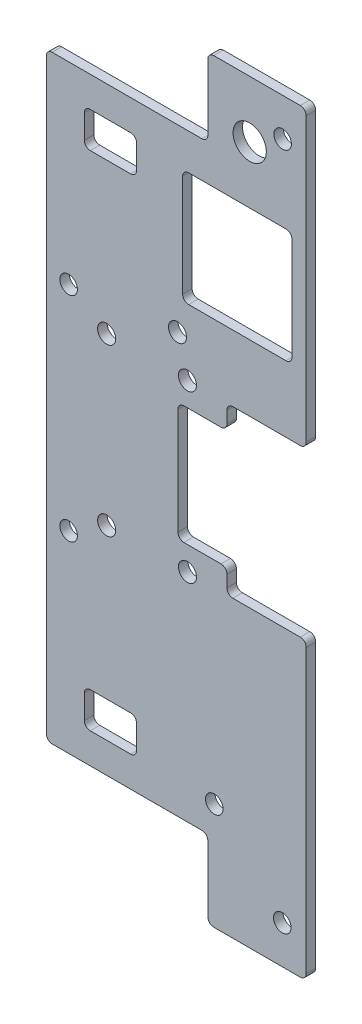
SolidWorks part; units mm, degrees
material "Thornel Mat VMA"
ref_plane "Front Plane" through (0, 0, 0) normal (0, 0, 1) x (1, 0, 0)
ref_plane "Top Plane" through (0, 0, 0) normal (0, 1, 0) x (1, 0, 0)
ref_plane "Right Plane" through (0, 0, 0) normal (1, 0, 0) x (0, 0, -1)
sketch "Sketch1" plane through (0, 0, 0) normal (0, 0, 1) x (1, 0, 0)
  line L0 (-2.9301, -104.5098) -> (-3.3149, -104.5098)
  line L1 (-3.3149, -72.8868) -> (-2.9301, -72.8868)
  line L78 (45.3299, -66.5368) -> (45.3299, -72.8868)
  line L79 (45.3299, -104.5098) -> (45.3299, -110.8598)
  line L80 (66.5174, -66.5368) -> (105.3971, 12.1397)
  line L81 (105.3971, 12.1397) -> (38.7094, 12.1397)
  line L88 (38.7094, 12.1397) -> (38.7094, -8.6883)
  line L89 (-2.9301, -8.6883) -> (38.7094, -8.6883)
  line L90 (-3.3149, -53.8368) -> (-2.9301, -53.8368)
  line L91 (-2.9301, -53.8368) -> (-2.9301, -8.6883)
  line L92 (-3.3149, -66.5368) -> (-3.3149, -53.8368)
  line L93 (-3.3149, -72.8868) -> (-3.3149, -66.5368)
  line L94 (-2.9301, -104.5098) -> (-2.9301, -72.8868)
  line L95 (-3.3149, -110.8598) -> (-3.3149, -104.5098)
  line L96 (66.5174, -110.8598) -> (105.3971, -189.5363)
  line L97 (105.3971, -189.5363) -> (38.7094, -189.5363)
  line L98 (38.7094, -189.5363) -> (38.7094, -168.7083)
  line L99 (-2.9301, -168.7083) -> (38.7094, -168.7083)
  line L106 (-3.3149, -110.8598) -> (-3.3149, -123.5598)
  line L107 (-3.3149, -123.5598) -> (-2.9301, -123.5598)
  line L108 (66.5174, -110.8598) -> (45.3299, -110.8598)
  line L109 (45.3299, -66.5368) -> (66.5174, -66.5368)
  line L110 (45.3299, -104.5098) -> (45.3299, -72.8868)
  line L111 (-2.9301, -123.5598) -> (-2.9301, -168.7083)
  circle A0 centre (90.6739, 2.6147) radius 2.3495
  circle A1 centre (41.9566, -16.4353) radius 2.3495
  circle A2 centre (3.0351, -60.1868) radius 2.3495
  circle A3 centre (3.0351, -117.2098) radius 2.3495
  circle A4 centre (41.9566, -160.9613) radius 2.3495
  circle A5 centre (90.6739, -180.0113) radius 2.3495
  circle A6 centre (51.4094, -3.1003) radius 4.445
  point P2 (90.6739, 2.6147)
  point P4 (41.9566, -16.4353)
  point P6 (3.0351, -60.1868)
  point P8 (3.0351, -117.2098)
  point P10 (41.9566, -160.9613)
  point P11 (90.6739, -180.0113)
  dimension "D2" = 4.699
  dimension "D5" = 8.89
  dimension "D1" = 66.6876
  dimension "D3" = 12.7
  dimension "D4" = 15.24
  dimension "D6" = 48.26
extrude "Boss-Extrude1" add sketch "Sketch1" along normal blind 2.54
sketch "Sketch2" plane through (0, 0, 2.54) normal (0, 0, 1) x (1, 0, 0)
  line L0 (-3.3149, -53.8368) -> (-3.3149, -72.8868) construction
  line L1 (45.3299, -66.5368) -> (66.5174, -66.5368) construction
  line L2 (45.3299, -88.6983) -> (-2.9301, -88.6983) construction
  line L3 (45.3299, -110.8598) -> (45.3299, -66.5368) construction
  line L4 (-2.9301, -72.8868) -> (-2.9301, -104.5098) construction
  circle A0 centre (13.1951, -66.5368) radius 2.413
  circle A2 centre (34.7851, -66.5368) radius 2.413
  circle A4 centre (34.7851, -110.8598) radius 2.413
  circle A6 centre (13.1951, -110.8598) radius 2.413
  dimension "D1" = 4.826
  dimension "D2" = 21.59
  dimension "D3" = 4.826
  dimension "D5" = 16.51
  dimension "D7" = 0
extrude "Cut-Extrude1" cut sketch "Sketch2" against normal through all
sketch "Sketch3" plane through (0, 0, 2.54) normal (0, 0, 1) x (1, 0, 0)
  line L0 (45.3299, -110.8598) -> (45.3299, -66.5368) construction
  line L1 (45.3299, -72.8868) -> (32.2451, -72.8868)
  line L2 (45.3299, -72.8868) -> (45.3299, -104.5098)
  line L3 (45.3299, -104.5098) -> (32.2451, -104.5098)
  line L4 (32.2451, -72.8868) -> (32.2451, -104.5098)
  line L5 (45.3299, -66.5368) -> (66.5174, -66.5368) construction
  line L6 (66.5174, -110.8598) -> (45.3299, -110.8598) construction
  circle A1 centre (13.1951, -66.5368) radius 2.413 construction
  dimension "D3" = 19.05
  dimension "D1" = 6.35
  dimension "D2" = 6.35
extrude "Cut-Extrude2" cut sketch "Sketch3" against normal through all
sketch "Sketch4" plane through (0, 0, 2.54) normal (0, 0, 1) x (1, 0, 0)
  line L0 (-2.9301, -168.7083) -> (38.7094, -168.7083) construction
  line L1 (27.4577, 15.7469) -> (40.2334, 15.7469)
  line L2 (27.4577, 15.7469) -> (27.4577, -8.6883)
  line L3 (27.4577, -8.6883) -> (40.2334, -8.6883)
  line L4 (40.2334, 15.7469) -> (40.2334, -8.6883)
  line L5 (0, -197.042) -> (40.2334, -197.042)
  line L6 (0, -197.042) -> (0, -168.7083)
  line L7 (0, -168.7083) -> (40.2334, -168.7083)
  line L8 (40.2334, -197.042) -> (40.2334, -168.7083)
  line L9 (38.7094, -168.7083) -> (38.7094, -189.5363) construction
  line L10 (38.7094, -8.6883) -> (-2.9301, -8.6883) construction
  dimension "D1" = 1.524
extrude "Cut-Extrude3" cut sketch "Sketch4" against normal through all
sketch "Sketch5" plane through (0, 0, 0) normal (0, 0, -1) x (-1, 0, 0)
  line L0 (2.9301, -8.6883) -> (2.9301, -53.8368) construction
  line L1 (-40.2334, -8.6883) -> (2.9301, -8.6883) construction
  circle A0 centre (-32.1219, -22.4043) radius 2.413
  circle A1 centre (-32.1219, -56.6943) radius 2.413
  dimension "D4" = 4.826
  dimension "D1" = 35.052
  dimension "D2" = 13.716
  dimension "D3" = 34.29
extrude "Cut-Extrude4" cut sketch "Sketch5" against normal through all
sketch "Sketch7" plane through (0, 0, 2.54) normal (0, 0, 1) x (1, 0, 0)
  line L0 (66.5174, -66.5368) -> (66.5174, 21.5221)
  line L1 (66.5174, 21.5221) -> (127.8208, 21.5221)
  line L2 (66.5174, -110.8598) -> (66.5174, -200.2563)
  line L3 (66.5174, -200.2563) -> (115.7822, -200.2563)
  line L4 (115.7822, -200.2563) -> (127.8208, 21.5221)
  line L5 (66.5174, -66.5368) -> (66.5174, -110.8598)
extrude "Cut-Extrude5" cut sketch "Sketch7" against normal through all both and the other way through all
extrude "Cut-Extrude6" cut sketch "Sketch8" against normal through all
sketch "Sketch8" plane through (7.0946, -169.3164, 0) normal (0, 0, -1) x (0.9999, -0.0134, 0)
  circle A0 centre (50.8264, -172.0317) radius 2.3495
  circle A1 centre (53.1547, 9.3081) radius 2.3495
fillet "Fillet1" radius 1.5875 16 edges at (-2.9301, -168.7083, 1.27) (40.2334, -168.7083, 1.27) (40.2334, -189.5363, 1.27) (66.5174, -189.5363, 1.27) (66.5174, -110.8598, 1.27) (45.3299, -110.8598, 1.27) (45.3299, -104.5098, 1.27) (32.2451, -104.5098, 1.27) (32.2451, -72.8868, 1.27) (45.3299, -72.8868, 1.27) (45.3299, -66.5368, 1.27) (66.5174, -66.5368, 1.27) (66.5174, 12.1397, 1.27) (40.2334, 12.1397, 1.27) (40.2334, -8.6883, 1.27) (-2.9301, -8.6883, 1.27)
sketch "Sketch9" plane through (0, -123.5598, 0) normal (0, -1, 0) x (1, 0, 0)
  line L1 (-3.3149, 2.54) -> (-2.9301, 2.54)
  line L2 (-3.3149, 2.54) -> (-3.3149, 0)
  line L3 (-3.3149, 0) -> (-2.9301, 0)
  line L4 (-2.9301, 2.54) -> (-2.9301, 0)
extrude "Cut-Extrude7" cut sketch "Sketch9" against normal through all
sketch "Sketch10" plane through (0, 0, 0) normal (0, 0, -1) x (-1, 0, 0)
  line L0 (-40.2334, -7.1008) -> (-40.2334, 10.5522) construction
  line L1 (-33.4974, -18.3403) -> (-62.7074, -18.3403)
  line L2 (-33.4974, -18.3403) -> (-33.4974, -48.8203)
  line L3 (-33.4974, -48.8203) -> (-62.7074, -48.8203)
  line L4 (-62.7074, -18.3403) -> (-62.7074, -48.8203)
  line L6 (-38.6459, -8.6883) -> (1.3426, -8.6883) construction
  line L7 (2.9301, -10.2758) -> (2.9301, -167.1208) construction
  line L8 (-7.2299, -16.8163) -> (-21.1999, -16.8163)
  line L9 (-7.2299, -16.8163) -> (-7.2299, -26.3413)
  line L10 (-7.2299, -26.3413) -> (-21.1999, -26.3413)
  line L11 (-21.1999, -16.8163) -> (-21.1999, -26.3413)
  line L12 (-32.2451, -88.6983) -> (2.9301, -88.6983) construction
  line L13 (-32.2451, -74.4743) -> (-32.2451, -102.9223) construction
  line L14 (-21.1999, -160.5803) -> (-21.1999, -151.0553)
  line L15 (-7.2299, -151.0553) -> (-21.1999, -151.0553)
  line L16 (-7.2299, -160.5803) -> (-7.2299, -151.0553)
  line L17 (-7.2299, -160.5803) -> (-21.1999, -160.5803)
  line L18 (-64.9299, 12.1397) -> (-41.8209, 12.1397) construction
  line L19 (-66.5174, 10.5522) -> (-66.5174, -64.9493) construction
  dimension "D1" = 30.48
  dimension "D2" = 29.21
  dimension "D3" = 8.128
  dimension "D4" = 9.525
  dimension "D5" = 10.16
  dimension "D6" = 13.97
  dimension "D7" = 30.48
  dimension "D8" = 3.81
extrude "Cut-Extrude8" cut sketch "Sketch10" against normal blind 2.54
sketch "Sketch12" plane through (0, 0, 0) normal (0, 0, -1) x (-1, 0, 0)
  line L0 (-46.5451, -18.3403) -> (-33.4974, -18.3403)
  line L1 (-43.3317, -18.3403) -> (-62.7074, -18.3403) construction
  line L2 (-33.4974, -18.3403) -> (-33.4974, -26.6795)
  line L3 (-33.4974, -48.8203) -> (-33.4974, -24.3869) construction
  line L4 (-33.4974, -26.6795) -> (-21.1999, -26.6795)
  line L5 (-21.1999, -16.8163) -> (-21.1999, -26.3413) construction
  line L6 (-21.1999, -26.6795) -> (-21.1999, -16.8163)
  line L7 (-21.1999, -16.8163) -> (-46.5451, -12.5328)
  line L8 (-46.5451, -12.5328) -> (-46.5451, -18.3403)
  line L9 (-33.8326, -104.5098) -> (-43.7424, -104.5098) construction
  line L10 (-40.1395, -107.4088) -> (-27.7341, -107.4088)
  line L11 (-40.1395, -107.4088) -> (-40.1395, -114.3781)
  line L12 (-40.1395, -114.3781) -> (-27.7341, -114.3781)
  line L13 (-27.7341, -107.4088) -> (-27.7341, -114.3781)
  line L14 (-45.3299, -109.2723) -> (-45.3299, -106.0973) construction
  dimension "D1" = 5.8075
  dimension "D2" = 8.3393
  dimension "D3" = 25.3451
  dimension "D4" = 12.4054
  dimension "D5" = 6.9693
  dimension "D6" = 2.899
  dimension "D7" = 5.1904
extrude "Boss-Extrude2" add sketch "Sketch12" against normal up to surface (2.54 mm away) up to face at (14.2149, -21.5788, 2.54)
fillet "Fillet2" radius 1.5875 12 edges at (21.1999, -160.5803, 1.27) (21.1999, -151.0553, 1.27) (7.2299, -151.0553, 1.27) (7.2299, -160.5803, 1.27) (21.1999, -26.3413, 1.27) (21.1999, -16.8163, 1.27) (7.2299, -16.8163, 1.27) (7.2299, -26.3413, 1.27) (33.4974, -48.8203, 1.27) (33.4974, -18.3403, 1.27) (62.7074, -48.8203, 1.27) (62.7074, -18.3403, 1.27)
sketch "Sketch13" plane through (0, 0, 0) normal (0, 0, -1) x (-1, 0, 0)
  circle A0 centre (-34.7851, -110.8598) radius 2.413
  circle A2 centre (-34.7851, -66.5368) radius 2.413 construction
  circle A3 centre (-13.1951, -110.8598) radius 2.413 construction
  dimension "D1" = 0
  dimension "D3" = 4.826
  dimension "D2" = 0
extrude "Cut-Extrude9" cut sketch "Sketch13" against normal through all both and the other way through all
